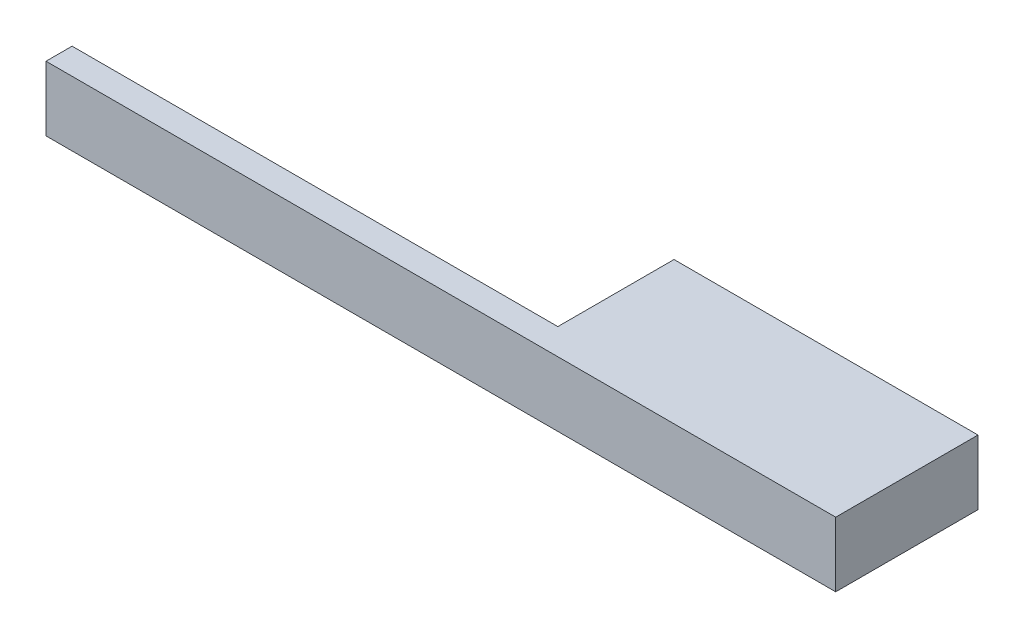
SolidWorks part; units mm, degrees
ref_plane "Front" through (0, 0, 0) normal (0, 0, 1) x (1, 0, 0)
ref_plane "Top" through (0, 0, 0) normal (0, 1, 0) x (1, 0, 0)
ref_plane "Right" through (0, 0, 0) normal (1, 0, 0) x (0, 0, -1)
sketch "Sketch1" plane through (0, 0, 0) normal (0, 1, 0) x (1, 0, 0)
  line L1 (0, 0) -> (47, 0)
  line L2 (0, 0) -> (0, 22)
  line L3 (0, 22) -> (47, 22)
  line L4 (47, 0) -> (47, 22)
  dimension "D1" = 47
  dimension "D2" = 22
extrude "Boss-Extrude1" add sketch "Sketch1" along normal blind 10
sketch "Sketch2" plane through (0, 0, 0) normal (-1, 0, 0) x (0, 0, 1)
  line L0 (-22, 0) -> (0, 0) construction
  line L1 (-4.0357, 0) -> (0, 0)
  line L2 (-4.0357, 0) -> (-4.0357, 10)
  line L3 (-4.0357, 10) -> (0, 10)
  line L4 (0, 0) -> (0, 10)
  line L5 (0, 10) -> (0, 0) construction
extrude "Boss-Extrude2" add sketch "Sketch2" along normal blind 75.1
